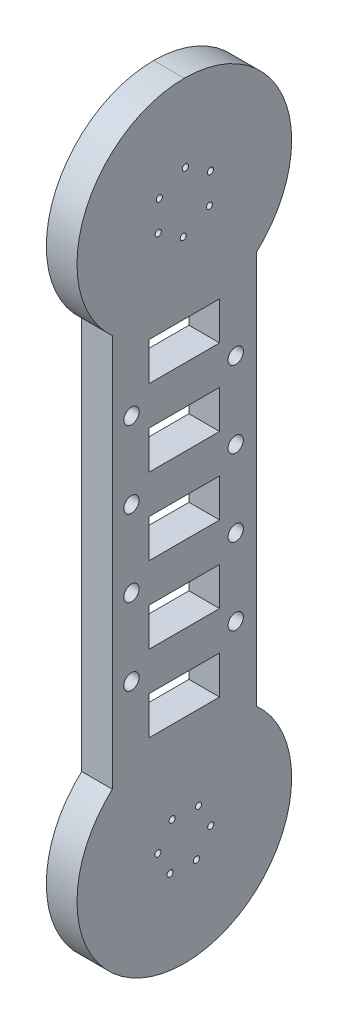
SolidWorks part; units mm, degrees
ref_plane "前视基准面" through (0, 0, 0) normal (0, 0, 1) x (1, 0, 0)
ref_plane "上视基准面" through (0, 0, 0) normal (0, 1, 0) x (1, 0, 0)
ref_plane "右视基准面" through (0, 0, 0) normal (1, 0, 0) x (0, 0, -1)
sketch "草图2" plane through (0, 0, 0) normal (0, 1, 0) x (1, 0, 0)
  line L1 (-70, -70) -> (70, -70)
  line L2 (-70, -70) -> (-70, 70)
  line L3 (-70, 70) -> (70, 70)
  line L4 (70, -70) -> (70, 70)
  line L5 (-70, -70) -> (70, 70) construction
  line L6 (-70, 70) -> (70, -70) construction
  point P0 (0, 0)
extrude "凸台-拉伸1" add sketch "草图2" along normal blind 500
fillet "圆角1" radius 70 2 edges at (0, 500, -70) (0, 500, 70)
fillet "圆角2" radius 70 2 edges at (0, 0, 70) (0, 0, -70)
sketch "草图5" plane through (0, 0, 70) normal (0, 0, 1) x (1, 0, 0)
  line L0 (-50, 360) -> (-50, 501.2854)
  line L5 (6.2704, 263.7949) -> (50, 360) construction
  line L6 (-50, 360) -> (-6.2704, 263.7949) construction
  line L7 (6.2704, 263.7949) -> (6.2704, 0.0207) construction
  line L8 (-6.2704, 263.7949) -> (-6.2704, 0.0207) construction
  line L9 (-6.2704, 0.0207) -> (6.2704, 0.0207) construction
  line L10 (50, 360) -> (50, 501.2854)
  line L11 (50, 501.2854) -> (-50, 501.2854)
  line L12 (6.2704, 263.7949) -> (-6.2704, 263.7949) construction
  line L13 (-50, 360) -> (50, 360)
  line L14 (-70, 500) -> (70, 0) construction
  point P0 (0, 250)
extrude "切除-拉伸2" cut sketch "草图5" against normal blind 300
sketch "草图6" plane through (70, 0, 0) normal (1, 0, 0) x (0, 0, -1)
  line L0 (-70, 250) -> (70, 250) construction
  line L1 (70, 70) -> (-70, 70) construction
  circle A0 centre (0, 430) radius 80
  circle A1 centre (0, 70) radius 80
extrude "切除-拉伸3" cut sketch "草图6" against normal blind 100 from offset 20 offset against normal yes
sketch "草图8" plane through (0, 0, 70) normal (0, 0, 1) x (1, 0, 0)
  line L0 (-50, 0) -> (-50, 420)
  line L1 (-50, 420) -> (50, 420)
  line L2 (50, 420) -> (50, 0)
  line L3 (50, 0) -> (-50, 0)
extrude "切除-拉伸4" cut sketch "草图8" against normal blind 188
sketch "草图9" plane through (-70, 0, 0) normal (-1, 0, 0) x (0, 0, 1)
  line L0 (-70, 430) -> (-70, 70)
  line L1 (-46.9593, 378.0883) -> (-46.9593, 121.9117)
  line L2 (46.9593, 378.0883) -> (46.9593, 121.9117)
  line L4 (70, 430) -> (70, 70)
  arc A2 (-46.9593, 378.0883) -> (-70, 430) centre (0, 430) cw
  arc A4 (46.9593, 121.9117) -> (70, 70) centre (0, 70) cw
  arc A5 (46.9593, 378.0883) -> (70, 430) centre (0, 430) ccw
  arc A7 (-70, 70) -> (-46.9593, 121.9117) centre (0, 70) cw
extrude "切除-拉伸6" cut sketch "草图9" against normal blind 185
sketch "草图10" plane through (70, 0, 0) normal (1, 0, 0) x (0, 0, -1)
  line L0 (-23, 313.9027) -> (-23, 288.9899)
  line L1 (-23, 363.9027) -> (23, 363.9027)
  line L2 (-23, 363.9027) -> (-23, 338.9899)
  line L3 (-23, 338.9899) -> (23, 338.9899)
  line L4 (23, 363.9027) -> (23, 338.9899)
  line L5 (-23, 313.9027) -> (23, 313.9027)
  line L6 (23, 313.9027) -> (23, 288.9899)
  line L7 (-23, 288.9899) -> (23, 288.9899)
  line L8 (-23, 263.9027) -> (-23, 238.9899)
  line L9 (-23, 263.9027) -> (23, 263.9027)
  line L10 (23, 263.9027) -> (23, 238.9899)
  line L11 (-23, 238.9899) -> (23, 238.9899)
  line L12 (-23, 213.9027) -> (-23, 188.9899)
  line L13 (-23, 213.9027) -> (23, 213.9027)
  line L14 (23, 213.9027) -> (23, 188.9899)
  line L15 (-23, 188.9899) -> (23, 188.9899)
  line L16 (-23, 163.9027) -> (-23, 138.9899)
  line L17 (-23, 163.9027) -> (23, 163.9027)
  line L18 (23, 163.9027) -> (23, 138.9899)
  line L19 (-23, 138.9899) -> (23, 138.9899)
  dimension "D1" = 5
extrude "切除-拉伸7" cut sketch "草图10" against normal blind 185
sketch "草图12" plane through (0, 0, -46.9593) normal (0, 0, -1) x (-1, 0, 0)
  line L1 (-87.5116, 517.6327) -> (-16.5397, 517.6327)
  line L2 (-87.5116, 517.6327) -> (-87.5116, -17.6327)
  line L3 (-87.5116, -17.6327) -> (-16.5397, -17.6327)
  line L4 (-16.5397, 517.6327) -> (-16.5397, -17.6327)
extrude "切除-拉伸9" cut sketch "草图12" against normal blind 192 and the other way blind 192
sketch "草图13" plane through (-70, 0, 0) normal (-1, 0, 0) x (0, 0, 1)
  circle A0 centre (-33.5074, 326.5278) radius 5
  circle A1 centre (34.4926, 326.5278) radius 5
  circle A2 centre (-33.5074, 276.5278) radius 5
  circle A3 centre (-33.5074, 226.5278) radius 5
  circle A4 centre (-33.5074, 176.5278) radius 5
  circle A5 centre (34.4926, 276.5278) radius 5
  circle A6 centre (34.4926, 226.5278) radius 5
  circle A7 centre (34.4926, 176.5278) radius 5
  dimension "D1" = 2
  dimension "D2" = 4
extrude "切除-拉伸10" cut sketch "草图13" against normal blind 192
sketch "草图15" plane through (-70, 0, 0) normal (-1, 0, 0) x (0, 0, 1)
  circle A0 centre (0, 70) radius 29.5
extrude "切除-拉伸11" cut sketch "草图15" against normal blind 10
sketch "草图17" plane through (-60, 0, 0) normal (-1, 0, 0) x (0, 0, 1)
  circle A0 centre (-9.288, 84.536) radius 2
  circle A1 centre (7.9446, 85.3116) radius 2
  circle A2 centre (17.2326, 70.7756) radius 2
  circle A3 centre (9.288, 55.464) radius 2
  circle A4 centre (-7.9446, 54.6884) radius 2
  circle A5 centre (-17.2326, 69.2244) radius 2
  point P2 (0, 68.5925)
  point P3 (0, 0)
  point P14 (0, 70)
  point P15 (-8.8197, 85.471)
  point P16 (0, 69.0433)
  point P17 (0, 71.2995)
  point P18 (0, 0)
  point P19 (0, 68.4734)
  dimension "D1" = 6
  dimension "D2" = 17.25
extrude "切除-拉伸12" cut sketch "草图17" against normal blind 10
sketch "草图18" plane through (-70, 0, 0) normal (-1, 0, 0) x (0, 0, 1)
  circle A0 centre (0, 430) radius 29.5
extrude "切除-拉伸14" cut sketch "草图18" against normal blind 10
sketch "草图20" plane through (-60, 0, 0) normal (-1, 0, 0) x (0, 0, 1)
  circle A0 centre (-0.6979, 449.2373) radius 2
  circle A1 centre (16.3111, 440.2231) radius 2
  circle A2 centre (17.009, 420.9857) radius 2
  circle A3 centre (0.6979, 410.7627) radius 2
  circle A4 centre (-16.3111, 419.7769) radius 2
  circle A5 centre (-17.009, 439.0143) radius 2
  point P2 (0, 428.932)
  point P14 (0, 430)
  dimension "D1" = 6
  dimension "D2" = 19.25
extrude "切除-拉伸15" cut sketch "草图20" against normal blind 10
